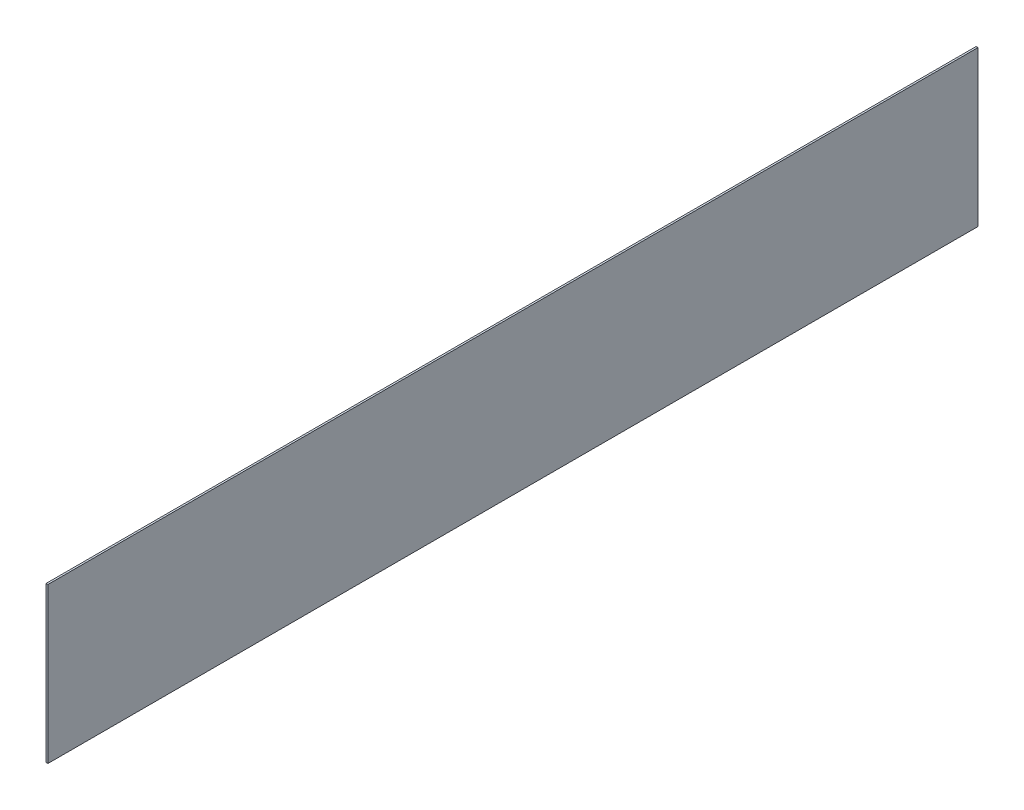
SolidWorks part; units mm, degrees
material "5052-H32"
ref_plane "Front Plane" through (0, 0, 0) normal (0, 0, 1) x (1, 0, 0)
ref_plane "Top Plane" through (0, 0, 0) normal (0, 1, 0) x (1, 0, 0)
ref_plane "Right Plane" through (0, 0, 0) normal (1, 0, 0) x (0, 0, -1)
sketch "Sketch1" plane through (0, 0, 0) normal (1, 0, 0) x (0, 0, -1)
  line L1 (-228.6, 76.2) -> (228.6, 76.2)
  line L2 (-228.6, 76.2) -> (-228.6, 0)
  line L3 (-228.6, 0) -> (228.6, 0)
  line L4 (228.6, 76.2) -> (228.6, 0)
  dimension "D1" = 457.2
  dimension "D2" = 76.2
extrude "Boss-Extrude1" add sketch "Sketch1" along normal mid plane 0.912
